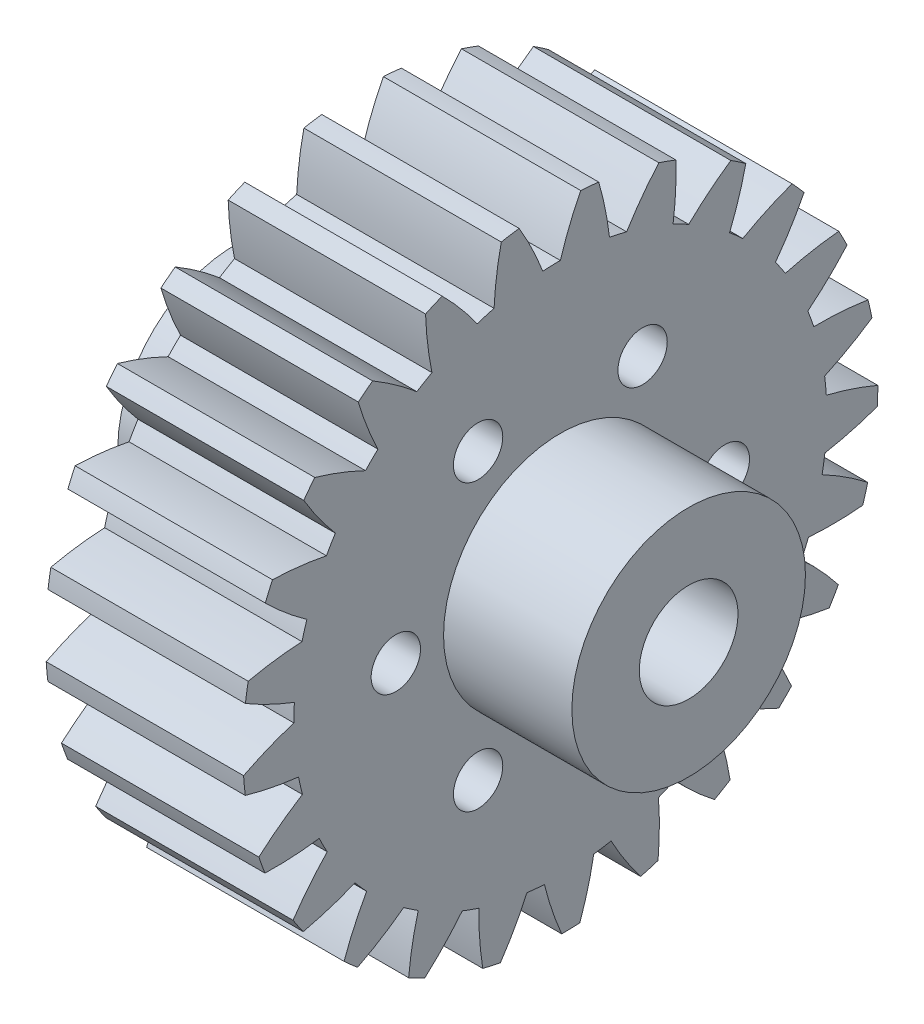
SolidWorks part; units mm, degrees
ref_plane "Front Plane" through (0, 0, 0) normal (0, 0, 1) x (1, 0, 0)
ref_plane "Top Plane" through (0, 0, 0) normal (0, 1, 0) x (1, 0, 0)
ref_plane "Right Plane" through (0, 0, 0) normal (1, 0, 0) x (0, 0, -1)
sketch "Sketch1" plane through (0, 0, 0) normal (1, 0, 0) x (0, 0, -1)
  line L0 (0, 0) -> (1.787, 19.2171) construction
  circle A1 centre (0, 0) radius 19.3 construction
  circle A3 centre (0, 0) radius 3
  arc A5 (1.2387, 19.2602) -> (2.3339, 19.1584) centre (0, 0) cw
  circle A6 centre (0, 0) radius 17.9 construction
  arc A105 (2.7, 17.6952) -> (0.6091, 17.8896) centre (0, 0) ccw
  arc A107 (0, 16.2) -> (1.2387, 19.2602) centre (18.6515, 10.4313) cw
  arc A109 (2.3339, 19.1584) -> (2.9871, 15.9222) centre (-16.4082, 13.6916) cw
  arc A111 (15.4071, 5.0061) -> (15.0442, 6.0095) centre (0, 0) ccw
  arc A113 (7.0251, 17.976) -> (6.853, 14.6791) centre (-12.4878, 17.342) cw
  arc A115 (5.9896, 18.3471) -> (7.0251, 17.976) centre (0, 0) cw
  arc A117 (4.0288, 15.691) -> (5.9896, 18.3471) centre (20.6596, 5.4651) cw
  arc A118 (11.2749, 15.6642) -> (10.2882, 12.5137) centre (-7.7827, 19.9027) cw
  arc A120 (10.3641, 16.2811) -> (11.2749, 15.6642) centre (0, 0) cw
  arc A122 (7.8044, 14.1962) -> (10.3641, 16.2811) centre (21.3697, 0.1556) cw
  arc A124 (14.8162, 12.3681) -> (13.077, 9.562) centre (-2.5886, 21.2129) cw
  arc A126 (14.0875, 13.1922) -> (14.8162, 12.3681) centre (0, 0) cw
  arc A128 (11.0897, 11.8093) -> (14.0875, 13.1922) centre (20.737, -5.1637) cw
  arc A131 (17.4265, 8.2949) -> (15.0442, 6.0095) centre (2.7682, 21.1902) cw
  arc A132 (16.9256, 9.2743) -> (17.4265, 8.2949) centre (0, 0) cw
  arc A134 (13.6781, 8.6804) -> (16.9256, 9.2743) centre (18.8014, -10.1586) cw
  arc A136 (18.9419, 3.7005) -> (16.066, 2.0793) centre (7.951, 19.8361) cw
  arc A138 (18.7003, 4.7737) -> (18.9419, 3.7005) centre (0, 0) cw
  arc A140 (15.4071, 5.0061) -> (18.7003, 4.7737) centre (15.6844, -14.5151) cw
  arc A143 (19.2671, -1.1264) -> (16.0784, -1.9815) centre (12.6343, 17.2355) cw
  arc A145 (19.3, -0.0269) -> (19.2671, -1.1264) centre (0, 0) cw
  arc A146 (16.168, 1.0172) -> (19.3, -0.0269) centre (11.5818, -17.9597) cw
  arc A148 (18.3817, -5.8825) -> (15.0805, -5.9177) centre (16.5236, 13.5521) cw
  arc A150 (18.687, -4.8257) -> (18.3817, -5.8825) centre (0, 0) cw
  arc A153 (15.9131, -3.0356) -> (18.687, -4.8257) centre (6.7516, -20.2757) cw
  arc A154 (16.3413, -10.2691) -> (13.135, -9.4822) centre (19.3748, 9.017) cw
  arc A155 (16.8998, -9.3214) -> (16.3413, -10.2691) centre (0, 0) cw
  arc A156 (14.6582, -6.8976) -> (16.8998, -9.3214) centre (1.4971, -21.3178) cw
  arc A157 (13.2741, -14.0103) -> (10.3642, -12.4508) centre (21.0085, 3.9154) cw
  arc A158 (14.0507, -13.2313) -> (13.2741, -14.0103) centre (0, 0) cw
  arc A159 (12.4823, -10.3263) -> (14.0507, -13.2313) centre (-3.8514, -21.0203) cw
  arc A160 (9.3728, -16.8713) -> (6.9422, -14.6371) centre (21.3222, -1.4322) cw
  arc A161 (10.3188, -16.3099) -> (9.3728, -16.8713) centre (0, 0) cw
  arc A162 (9.5221, -13.1061) -> (10.3188, -16.3099) centre (-8.958, -19.4021) cw
  arc A163 (4.8826, -18.6722) -> (3.084, -15.9037) centre (20.2962, -6.6898) cw
  arc A164 (5.9385, -18.3637) -> (4.8826, -18.6722) centre (0, 0) cw
  arc A165 (5.9636, -15.0624) -> (5.9385, -18.3637) centre (-13.5017, -16.5648) cw
  arc A166 (0.0856, -19.2998) -> (-0.968, -16.1711) centre (17.9949, -11.5271) cw
  arc A167 (1.185, -19.2636) -> (0.0856, -19.2998) centre (0, 0) cw
  arc A168 (2.0304, -16.0723) -> (1.185, -19.2636) centre (-17.197, -12.6867) cw
  arc A169 (-4.7167, -18.7148) -> (-4.9591, -15.4223) centre (14.5628, -15.6401) cw
  arc A170 (-3.6429, -18.9531) -> (-4.7167, -18.7148) centre (0, 0) cw
  arc A171 (-2.0304, -16.0723) -> (-3.6429, -18.9531) centre (-19.8118, -8.0114) cw
  arc A172 (-9.2227, -16.9538) -> (-8.6387, -13.7045) centre (10.2158, -18.7704) cw
  arc A173 (-8.2418, -17.4517) -> (-9.2227, -16.9538) centre (0, 0) cw
  arc A174 (-5.9636, -15.0624) -> (-8.2418, -17.4517) centre (-21.1817, -2.8327) cw
  arc A175 (-13.1492, -14.1276) -> (-11.7755, -11.1256) centre (5.2268, -20.7212) cw
  arc A176 (-12.323, -14.8538) -> (-13.1492, -14.1276) centre (0, 0) cw
  arc A177 (-9.5221, -13.1061) -> (-12.323, -14.8538) centre (-21.2207, 2.524) cw
  arc A178 (-16.2495, -10.4137) -> (-14.1723, -7.8476) centre (-0.0905, -21.3701) cw
  arc A179 (-15.6298, -11.3225) -> (-16.2495, -10.4137) centre (0, 0) cw
  arc A180 (-12.4823, -10.3263) -> (-15.6298, -11.3225) centre (-19.9263, 7.722) cw
  arc A181 (-18.3287, -6.0454) -> (-15.6787, -4.0765) centre (-5.4022, -20.6762) cw
  arc A182 (-17.9546, -7.0798) -> (-18.3287, -6.0454) centre (0, 0) cw
  arc A183 (-14.6582, -6.8976) -> (-17.9546, -7.0798) centre (-17.3799, 12.4349) cw
  arc A184 (-19.2563, -1.2973) -> (-16.1999, -0.0493) centre (-10.3744, -18.6831) cw
  arc A185 (-19.1512, -2.3923) -> (-19.2563, -1.2973) centre (0, 0) cw
  arc A186 (-15.9131, -3.0356) -> (-19.1512, -2.3923) centre (-13.7415, 16.3665) cw
  arc A187 (-18.974, 3.5323) -> (-15.7032, 3.981) centre (-14.6948, -15.5161) cw
  arc A188 (-19.1444, 2.4456) -> (-18.974, 3.5323) centre (0, 0) cw
  arc A189 (-16.168, 1.0172) -> (-19.1444, 2.4456) centre (-9.2396, 19.2696) cw
  arc A190 (-17.4995, 8.14) -> (-14.2199, 7.7611) centre (-18.0919, -11.3742) cw
  arc A191 (-17.9348, 7.1298) -> (-17.4995, 8.14) centre (0, 0) cw
  arc A192 (-15.4071, 5.0061) -> (-17.9348, 7.1298) centre (-4.1571, 20.962) cw
  arc A193 (-14.9253, 12.2362) -> (-11.843, 11.0537) centre (-20.3521, -6.5176) cw
  arc A194 (-15.5982, 11.366) -> (-14.9253, 12.2362) centre (0, 0) cw
  arc A195 (-13.6781, 8.6804) -> (-15.5982, 11.366) centre (1.1865, 21.3373) cw
  arc A196 (-11.4134, 15.5635) -> (-8.722, 13.6516) centre (-21.3336, -1.2515) cw
  arc A197 (-12.2816, 14.888) -> (-11.4134, 15.5635) centre (0, 0) cw
  arc A198 (-11.0897, 11.8093) -> (-12.2816, 14.888) centre (6.4556, 20.3719) cw
  arc A199 (-7.1844, 17.913) -> (-5.053, 15.3918) centre (-20.9746, 4.0933) cw
  arc A200 (-8.1932, 17.4746) -> (-7.1844, 17.913) centre (0, 0) cw
  arc A201 (-7.8044, 14.1962) -> (-8.1932, 17.4746) centre (11.3191, 18.1264) cw
  arc A202 (-2.5039, 19.1369) -> (-1.0664, 16.1649) centre (-19.2977, 9.1809) cw
  arc A203 (-3.5901, 18.9632) -> (-2.5039, 19.1369) centre (0, 0) cw
  arc A204 (-4.0288, 15.691) -> (-3.5901, 18.9632) centre (15.4713, 14.742) cw
  arc A205 (13.6781, 8.6804) -> (13.077, 9.562) centre (0, 0) ccw
  arc A206 (11.0897, 11.8093) -> (10.2882, 12.5137) centre (0, 0) ccw
  arc A207 (7.8044, 14.1962) -> (6.853, 14.6791) centre (0, 0) ccw
  arc A208 (4.0288, 15.691) -> (2.9871, 15.9222) centre (0, 0) ccw
  arc A209 (16.168, 1.0172) -> (16.066, 2.0793) centre (0, 0) ccw
  arc A210 (15.9131, -3.0356) -> (16.0784, -1.9815) centre (0, 0) ccw
  arc A211 (14.6582, -6.8976) -> (15.0805, -5.9177) centre (0, 0) ccw
  arc A212 (12.4823, -10.3263) -> (13.135, -9.4822) centre (0, 0) ccw
  arc A213 (9.5221, -13.1061) -> (10.3642, -12.4508) centre (0, 0) ccw
  arc A214 (5.9636, -15.0624) -> (6.9422, -14.6371) centre (0, 0) ccw
  arc A215 (2.0304, -16.0723) -> (3.084, -15.9037) centre (0, 0) ccw
  arc A216 (-2.0304, -16.0723) -> (-0.968, -16.1711) centre (0, 0) ccw
  arc A217 (-5.9636, -15.0624) -> (-4.9591, -15.4223) centre (0, 0) ccw
  arc A218 (-9.5221, -13.1061) -> (-8.6387, -13.7045) centre (0, 0) ccw
  arc A219 (-12.4823, -10.3263) -> (-11.7755, -11.1256) centre (0, 0) ccw
  arc A220 (-14.6582, -6.8976) -> (-14.1723, -7.8476) centre (0, 0) ccw
  arc A221 (-15.9131, -3.0356) -> (-15.6787, -4.0765) centre (0, 0) ccw
  arc A222 (-16.168, 1.0172) -> (-16.1999, -0.0493) centre (0, 0) ccw
  arc A223 (-15.4071, 5.0061) -> (-15.7032, 3.981) centre (0, 0) ccw
  arc A224 (-13.6781, 8.6804) -> (-14.2199, 7.7611) centre (0, 0) ccw
  arc A225 (-4.0288, 15.691) -> (-5.053, 15.3918) centre (0, 0) ccw
  arc A226 (-7.8044, 14.1962) -> (-8.722, 13.6516) centre (0, 0) ccw
  arc A227 (-11.0897, 11.8093) -> (-11.843, 11.0537) centre (0, 0) ccw
  arc A228 (0, 16.2) -> (-1.0664, 16.1649) centre (0, 0) ccw
  circle A229 centre (0, 0) radius 10 construction
  circle A230 centre (10, 0) radius 1.5
  circle A231 centre (5, -8.6603) radius 1.5
  circle A232 centre (-5, -8.6603) radius 1.5
  circle A233 centre (-10, 0) radius 1.5
  circle A234 centre (-5, 8.6603) radius 1.5
  circle A235 centre (5, 8.6603) radius 1.5
  point P10 (1.787, 19.2171)
  point P13 (1.6574, 17.8231)
  point P160 (0, 0)
  point P165 (0, 0)
  point P177 (0, 0)
  dimension "D1" = 32.4
  dimension "D2" = 38.6
  dimension "D3" = 6
  dimension "D4" = 3
  dimension "D6" = 2.1
  dimension "D7" = 35.8
  dimension "D5" = 1.1
extrude "Boss-Extrude1" add sketch "Sketch1" along normal blind 12 contours A107 A228 A202 A203 A204 A225 A199 A200 A201 A226 A196 A197 A198 A227 A193 A194 A195 A224 A190 A191 A192 A223 A187 A188 A189 A222 A184 A185 A186 A221 A181 A182 A183 A220 A178 A179 A180 A219 A175 A176 A177 A218 A172 A173 A174 A217 A169 A170 A171 A216 A166 | A109 A5 A107 A105 region at (0, 18.4419, -1.7149) region at (0, 17.281, -1.607)
sketch "Sketch2" plane through (12, 0, 0) normal (1, 0, 0) x (0, 0, -1)
  circle A0 centre (0, 0) radius 7.1
  circle A1 centre (0, 0) radius 3
  dimension "D1" = 6
  dimension "D2" = 14.2
extrude "Boss-Extrude2" add sketch "Sketch2" along normal blind 7.8 and the other way blind 19.8
